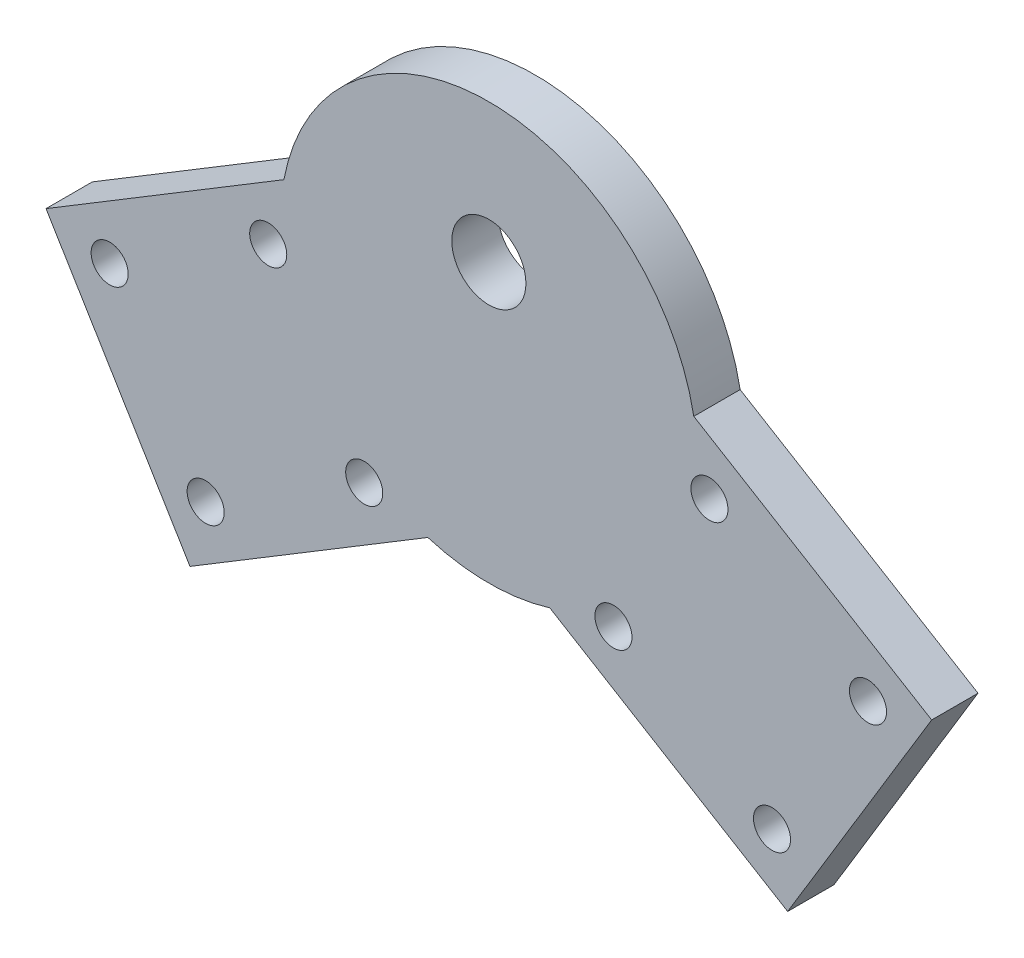
SolidWorks part; units mm, degrees
ref_plane "Front Plane" through (0, 0, 0) normal (0, 0, 1) x (1, 0, 0)
ref_plane "Top Plane" through (0, 0, 0) normal (0, 1, 0) x (1, 0, 0)
ref_plane "Right Plane" through (0, 0, 0) normal (1, 0, 0) x (0, 0, -1)
sketch "Sketch2" plane through (0, 0, 0) normal (0, 0, 1) x (1, 0, 0)
  line L8 (0, 0) -> (0, -22.5) construction
  line L9 (0, 0) -> (6.5784, -21.5169)
  line L10 (0, 0) -> (-6.5784, -21.5169)
  line L11 (6.5784, -21.5169) -> (22.1146, 4.1469)
  line L12 (6.5784, -21.5169) -> (32.2421, -37.053)
  line L13 (22.1146, 4.1469) -> (47.7783, -11.3893)
  line L14 (32.2421, -37.053) -> (47.7783, -11.3893)
  line L15 (-6.5784, -21.5169) -> (-22.1146, 4.1469)
  line L16 (-6.5784, -21.5169) -> (-32.2421, -37.053)
  line L17 (-22.1146, 4.1469) -> (-47.7783, -11.3893)
  line L18 (-32.2421, -37.053) -> (-47.7783, -11.3893)
  circle A0 centre (0, 0) radius 22.5
  dimension "D5" = 45
  dimension "D1" = 17
  dimension "D2" = 17
  dimension "D3" = 30
  dimension "D4" = 30
  dimension "D6" = 30
  dimension "D7" = 30
extrude "Boss-Extrude1" add sketch "Sketch2" along normal blind 5 contours A0 | L15 L16 L18 L17 | L11 L12 L14 L13
sketch "Sketch4" plane through (0, 0, 5) normal (0, 0, 1) x (1, 0, 0)
  line L0 (-22.1146, 4.1469) -> (-6.5784, -21.5169)
  line L1 (-22.1146, 4.1469) -> (-47.7783, -11.3893) construction
  line L2 (-6.5784, -21.5169) -> (-32.2421, -37.053) construction
  line L3 (-32.2421, -37.053) -> (-47.7783, -11.3893) construction
  line L4 (6.5784, -21.5169) -> (22.1146, 4.1469)
  line L5 (-40.9116, -13.0772) -> (-23.8025, -2.7198)
  line L6 (-23.8025, -2.7198) -> (-13.445, -19.8289)
  line L7 (6.5784, -21.5169) -> (32.2421, -37.053) construction
  line L8 (22.1146, 4.1469) -> (47.7783, -11.3893) construction
  line L9 (32.2421, -37.053) -> (47.7783, -11.3893) construction
  line L10 (-13.445, -19.8289) -> (-30.5542, -30.1864)
  line L11 (-30.5542, -30.1864) -> (-40.9116, -13.0772)
  line L12 (23.8025, -2.7198) -> (40.9116, -13.0772)
  line L13 (40.9116, -13.0772) -> (30.5542, -30.1864)
  line L14 (30.5542, -30.1864) -> (13.445, -19.8289)
  line L15 (13.445, -19.8289) -> (23.8025, -2.7198)
  line L16 (-41.7901, -7.7642) -> (-26.2539, -33.4279)
  line L17 (-45.2119, -9.8357) -> (-29.6757, -35.4994)
  line L18 (-46.2247, -13.9557) -> (-20.5609, 1.5805)
  line L19 (-44.1532, -17.3775) -> (-18.4894, -1.8413)
  line L20 (-24.6809, 2.5932) -> (-9.1447, -23.0705)
  line L21 (-28.1028, 0.5218) -> (-12.5666, -25.142)
  line L22 (-33.7957, -34.4867) -> (-8.132, -18.9505)
  line L23 (-35.8672, -31.0648) -> (-10.2035, -15.5287)
  line L24 (-33.3008, -29.5112) -> (-29.879, -27.4397)
  line L25 (-33.3008, -29.5112) -> (-31.2344, -32.9246)
  line L26 (-29.879, -27.4397) -> (-27.8126, -30.8531)
  line L27 (-31.2344, -32.9246) -> (-27.8126, -30.8531)
  circle A0 centre (-40.9116, -13.0772) radius 2
  circle A1 centre (-23.8025, -2.7198) radius 2
  circle A2 centre (-13.445, -19.8289) radius 2
  circle A3 centre (-30.5542, -30.1864) radius 2
  circle A4 centre (23.8025, -2.7198) radius 2
  circle A6 centre (13.445, -19.8289) radius 2
  circle A7 centre (40.9116, -13.0772) radius 2
  circle A8 centre (30.5542, -30.1864) radius 2
  dimension "D10" = 4
  dimension "D11" = 4
  dimension "D12" = 4
  dimension "D13" = 4
  dimension "D19" = 4
  dimension "D20" = 4
  dimension "D25" = 4
  dimension "D26" = 4
  dimension "D1" = 30
  dimension "D2" = 5
  dimension "D3" = 5
  dimension "D4" = 5
  dimension "D5" = 5
  dimension "D6" = 5
  dimension "D7" = 5
  dimension "D8" = 5
  dimension "D9" = 5
  dimension "D14" = 30
  dimension "D15" = 5
  dimension "D16" = 5
  dimension "D17" = 5
  dimension "D18" = 5
  dimension "D21" = 5
  dimension "D22" = 5
  dimension "D23" = 5
  dimension "D24" = 5
  dimension "D27" = 3
  dimension "D28" = 3
  dimension "D29" = 4
  dimension "D30" = 4
  dimension "D31" = 3
  dimension "D32" = 4
  dimension "D33" = 3
  dimension "D34" = 4
extrude "Cut-Extrude1" cut sketch "Sketch4" against normal blind 10 contours A0 | A1 | A2 | A3 | A6 | A4 | A7 | A8
sketch "Sketch5" plane through (0, 0, 5) normal (0, 0, 1) x (1, 0, 0)
  line L0 (0, 22.5) -> (0, -22.5)
  arc A0 (22.1146, 4.1469) -> (-22.1146, 4.1469) centre (0, 0) ccw construction
  arc A1 (-6.5784, -21.5169) -> (6.5784, -21.5169) centre (0, 0) ccw construction
  circle A2 centre (0, 7.5) radius 4
  dimension "D2" = 8
  dimension "D1" = 30
extrude "Cut-Extrude2" cut sketch "Sketch5" against normal blind 10 contours A2
